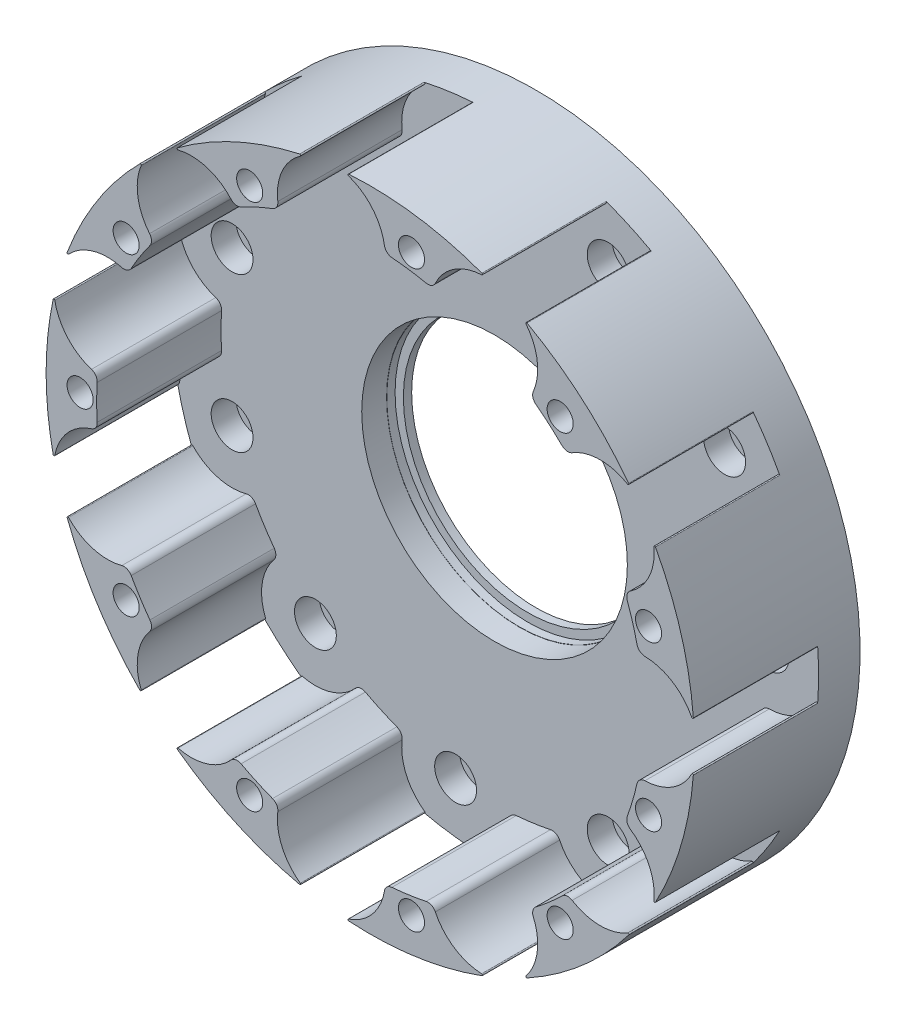
SolidWorks part; units mm, degrees
material "ABS"
ref_plane "Front Plane" through (0, 0, 0) normal (0, 0, 1) x (1, 0, 0)
ref_plane "Top Plane" through (0, 0, 0) normal (0, 1, 0) x (1, 0, 0)
ref_plane "Right Plane" through (0, 0, 0) normal (1, 0, 0) x (0, 0, -1)
sketch "Sketch1" plane through (0, 0, 0) normal (0, 0, 1) x (1, 0, 0)
  circle A0 centre (0, 0) radius 39.1
  circle A1 centre (0, 0) radius 33 construction
  circle A2 centre (33, 0) radius 2.525
  circle A3 centre (27.7614, -17.8411) radius 2.525
  circle A4 centre (13.7087, -30.0179) radius 2.525
  circle A5 centre (-4.6964, -32.6641) radius 2.525
  circle A6 centre (-21.6104, -24.9397) radius 2.525
  circle A7 centre (-31.6633, -9.2972) radius 2.525
  circle A8 centre (-31.6633, 9.2972) radius 2.525
  circle A9 centre (-21.6104, 24.9397) radius 2.525
  circle A10 centre (-4.6964, 32.6641) radius 2.525
  circle A11 centre (13.7087, 30.0179) radius 2.525
  circle A12 centre (27.7614, 17.8411) radius 2.525
  circle A13 centre (0, 0) radius 16.025
  point P28 (0, 0)
extrude "Boss-Extrude1" add sketch "Sketch1" along normal blind 3
sketch "Sketch2" plane through (0, 0, 0) normal (0, 0, -1) x (-1, 0, 0)
  circle A0 centre (0, 0) radius 16
  circle A1 centre (0, 0) radius 39.1
  circle A2 centre (0, 0) radius 39.1 construction
  dimension "D1" = 32
extrude "Boss-Extrude2" add sketch "Sketch2" along normal blind 2 contours A1 | A0
sketch "Sketch3" plane through (0, 0, 3) normal (0, 0, 1) x (1, 0, 0)
  circle A0 centre (33, 0) radius 1.6
  circle A1 centre (27.7614, -17.8411) radius 1.6
  circle A2 centre (13.7087, -30.0179) radius 1.6
  circle A3 centre (-4.6964, -32.6641) radius 1.6
  circle A4 centre (-21.6104, -24.9397) radius 1.6
  circle A5 centre (-31.6633, -9.2972) radius 1.6
  circle A6 centre (-31.6633, 9.2972) radius 1.6
  circle A7 centre (-21.6104, 24.9397) radius 1.6
  circle A8 centre (-4.6964, 32.6641) radius 1.6
  circle A9 centre (13.7087, 30.0179) radius 1.6
  circle A10 centre (27.7614, 17.8411) radius 1.6
  point P25 (0, 0)
  dimension "D1" = 3.2
  dimension "D2" = 11
sketch "Sketch4" plane through (0, 0, -2) normal (0, 0, -1) x (-1, 0, 0)
  circle A0 centre (0, 0) radius 16
  circle A1 centre (0, 0) radius 15
  dimension "D1" = 32
  dimension "D2" = 30
extrude "Boss-Extrude3" add sketch "Sketch4" against normal blind 1
sketch "Sketch5" plane through (0, 0, 3) normal (0, 0, 1) x (1, 0, 0)
  circle A0 centre (0, 0) radius 39.1
  circle A1 centre (0, 0) radius 39.1 construction
  arc A2 (1.7973, 32.951) -> (-11.0078, 31.1099) centre (-4.6964, 32.6641) ccw
  arc A3 (19.3266, 26.7485) -> (7.5589, 32.1226) centre (13.7087, 30.0179) ccw
  arc A4 (30.7199, 12.0535) -> (23.7258, 22.9366) centre (27.7614, 17.8411) ccw
  arc A5 (32.3598, -6.4684) -> (32.3598, 6.4684) centre (33, 0) ccw
  arc A6 (23.7258, -22.9366) -> (30.7199, -12.0535) centre (27.7614, -17.8411) ccw
  arc A7 (7.5589, -32.1226) -> (19.3266, -26.7485) centre (13.7087, -30.0179) ccw
  arc A8 (-11.0078, -31.1099) -> (1.7973, -32.951) centre (-4.6964, -32.6641) ccw
  arc A9 (-26.0797, -20.22) -> (-16.3027, -28.6918) centre (-21.6104, -24.9397) ccw
  arc A10 (-32.8714, -2.9104) -> (-29.2267, -15.3232) centre (-31.6633, -9.2972) ccw
  arc A11 (-29.2267, 15.3232) -> (-32.8714, 2.9104) centre (-31.6633, 9.2972) ccw
  arc A12 (-16.3027, 28.6918) -> (-26.0797, 20.22) centre (-21.6104, 24.9397) ccw
  arc A13 (-32.8714, 2.9104) -> (-32.8714, -2.9104) centre (0, 0) ccw
  arc A14 (-26.0797, 20.22) -> (-29.2267, 15.3232) centre (0, 0) ccw
  arc A15 (-11.0078, 31.1099) -> (-16.3027, 28.6918) centre (0, 0) ccw
  arc A16 (7.5589, 32.1226) -> (1.7973, 32.951) centre (0, 0) ccw
  arc A17 (23.7258, 22.9366) -> (19.3266, 26.7485) centre (0, 0) ccw
  arc A18 (32.3598, 6.4684) -> (30.7199, 12.0535) centre (0, 0) ccw
  arc A19 (30.7199, -12.0535) -> (32.3598, -6.4684) centre (0, 0) ccw
  arc A20 (19.3266, -26.7485) -> (23.7258, -22.9366) centre (0, 0) ccw
  arc A21 (1.7973, -32.951) -> (7.5589, -32.1226) centre (0, 0) ccw
  arc A22 (-16.3027, -28.6918) -> (-11.0078, -31.1099) centre (0, 0) ccw
  arc A23 (-29.2267, -15.3232) -> (-26.0797, -20.22) centre (0, 0) ccw
  point P30 (0, 0)
  dimension "D1" = 11
  dimension "D2" = 6.5
extrude "Boss-Extrude4" add sketch "Sketch5" along normal blind 15 contours A17 A4 A0 A3 | A18 A5 A0 A4 | A19 A6 A0 A5 | A20 A7 A0 A6 | A21 A8 A0 A7 | A22 A9 A0 A8 | A23 A10 A0 A9 | A13 A11 A0 A10 | A14 A12 A0 A11 | A15 A2 A0 A12 | A16 A3 A0 A2 region at (34.9977, 10.2762, 3) region at (34.9977, -10.2762, 3) region at (23.8862, 27.5661, 3) region at (23.8862, -27.5661, 3) region at (5.191, 36.1039, 3) region at (5.191, -36.1039, 3) region at (-15.1523, 33.179, 3) region at (-15.1523, -33.179, 3) region at (-30.6849, 19.72, 3) region at (-30.6849, -19.72, 3) region at (-36.4752, 0, 3)
fillet "Fillet1" radius 0.1 22 edges at (-7.9713, 38.2788, 10.5) (-27.401, 27.8926, 10.5) (-23.7091, 31.0916, 10.5) (-36.7548, 13.3378, 10.5) (-38.131, 8.6507, 10.5) (-38.131, -8.6507, 10.5) (-36.7548, -13.3378, 10.5) (-27.401, -27.8926, 10.5) (-23.7091, -31.0916, 10.5) (-7.9713, -38.2788, 10.5) (-3.136, -38.974, 10.5) (13.9892, -36.5118, 10.5) (18.4328, -34.4825, 10.5) (31.5083, -23.1525, 10.5) (34.1493, -19.043, 10.5) (39.0236, -2.4425, 10.5) (34.1493, 19.043, 10.5) (39.0236, 2.4425, 10.5) (31.5083, 23.1525, 10.5) (18.4328, 34.4825, 10.5) (13.9892, 36.5118, 10.5) (-3.136, 38.974, 10.5)
fillet "Fillet2" radius 1 22 edges at (-11.0078, -31.1099, 10.5) (-16.3027, -28.6918, 10.5) (23.7258, -22.9366, 10.5) (19.3266, -26.7485, 10.5) (7.5589, -32.1226, 10.5) (1.7973, -32.951, 10.5) (-29.2267, -15.3232, 10.5) (-26.0797, -20.22, 10.5) (-32.8714, -2.9104, 10.5) (-32.8714, 2.9104, 10.5) (-26.0797, 20.22, 10.5) (-29.2267, 15.3232, 10.5) (-16.3027, 28.6918, 10.5) (-11.0078, 31.1099, 10.5) (30.7199, -12.0535, 10.5) (32.3598, -6.4684, 10.5) (32.3598, 6.4684, 10.5) (30.7199, 12.0535, 10.5) (23.7258, 22.9366, 10.5) (19.3266, 26.7485, 10.5) (7.5589, 32.1226, 10.5) (1.7973, 32.951, 10.5)
sketch "Sketch7" plane through (0, 0, -2) normal (0, 0, -1) x (-1, 0, 0)
  line L0 (0, 0) -> (35, 0) construction
  circle A0 centre (35, 0) radius 1.575
  circle A1 centre (29.4439, -18.9224) radius 1.575
  circle A2 centre (14.5395, -31.8371) radius 1.575
  circle A3 centre (-4.981, -34.6438) radius 1.575
  circle A4 centre (-22.9201, -26.4512) radius 1.575
  circle A5 centre (-33.5823, -9.8606) radius 1.575
  circle A6 centre (-33.5823, 9.8606) radius 1.575
  circle A7 centre (-22.9201, 26.4512) radius 1.575
  circle A8 centre (-4.981, 34.6438) radius 1.575
  circle A9 centre (14.5395, 31.8371) radius 1.575
  circle A10 centre (29.4439, 18.9224) radius 1.575
  point P26 (0, 0)
  dimension "D2" = 3.15
  dimension "D1" = 35
  dimension "D3" = 11
extrude "Cut-Extrude1" cut sketch "Sketch7" against normal through all
sketch "Sketch8" plane through (0, 0, -2) normal (0, 0, -1) x (-1, 0, 0)
  line L0 (32.2124, -20.7016) -> (32.3689, -17.4145)
  line L1 (38.2909, 0) -> (36.6454, 2.85)
  line L2 (36.6454, 2.85) -> (33.3546, 2.85)
  line L3 (33.3546, 2.85) -> (31.7091, 0)
  line L4 (31.7091, 0) -> (33.3546, -2.85)
  line L5 (33.3546, -2.85) -> (36.6454, -2.85)
  line L6 (36.6454, -2.85) -> (38.2909, 0)
  line L7 (32.3689, -17.4145) -> (29.6005, -15.6353)
  line L8 (29.6005, -15.6353) -> (26.6754, -17.1432)
  line L9 (26.6754, -17.1432) -> (26.5188, -20.4304)
  line L10 (26.5188, -20.4304) -> (29.2873, -22.2096)
  line L11 (29.2873, -22.2096) -> (32.2124, -20.7016)
  line L12 (15.9066, -34.8306) -> (17.8155, -32.1499)
  line L13 (17.8155, -32.1499) -> (16.4484, -29.1564)
  line L14 (16.4484, -29.1564) -> (13.1724, -28.8436)
  line L15 (13.1724, -28.8436) -> (11.2635, -31.5243)
  line L16 (11.2635, -31.5243) -> (12.6306, -34.5178)
  line L17 (12.6306, -34.5178) -> (15.9066, -34.8306)
  line L18 (-5.4494, -37.9012) -> (-2.3942, -36.678)
  line L19 (-2.3942, -36.678) -> (-1.9259, -33.4206)
  line L20 (-1.9259, -33.4206) -> (-4.5127, -31.3864)
  line L21 (-4.5127, -31.3864) -> (-7.5678, -32.6095)
  line L22 (-7.5678, -32.6095) -> (-8.0362, -35.8669)
  line L23 (-8.0362, -35.8669) -> (-5.4494, -37.9012)
  line L24 (-25.0752, -28.9383) -> (-21.8438, -29.5611)
  line L25 (-21.8438, -29.5611) -> (-19.6887, -27.074)
  line L26 (-19.6887, -27.074) -> (-20.765, -23.9641)
  line L27 (-20.765, -23.9641) -> (-23.9965, -23.3413)
  line L28 (-23.9965, -23.3413) -> (-26.1516, -25.8284)
  line L29 (-26.1516, -25.8284) -> (-25.0752, -28.9383)
  line L30 (-36.7398, -10.7878) -> (-34.3581, -13.0588)
  line L31 (-34.3581, -13.0588) -> (-31.2005, -12.1316)
  line L32 (-31.2005, -12.1316) -> (-30.4247, -8.9335)
  line L33 (-30.4247, -8.9335) -> (-32.8064, -6.6625)
  line L34 (-32.8064, -6.6625) -> (-35.964, -7.5897)
  line L35 (-35.964, -7.5897) -> (-36.7398, -10.7878)
  line L36 (-36.7398, 10.7878) -> (-35.964, 7.5897)
  line L37 (-35.964, 7.5897) -> (-32.8064, 6.6625)
  line L38 (-32.8064, 6.6625) -> (-30.4247, 8.9335)
  line L39 (-30.4247, 8.9335) -> (-31.2005, 12.1316)
  line L40 (-31.2005, 12.1316) -> (-34.3581, 13.0588)
  line L41 (-34.3581, 13.0588) -> (-36.7398, 10.7878)
  line L42 (-25.0752, 28.9383) -> (-26.1516, 25.8284)
  line L43 (-26.1516, 25.8284) -> (-23.9965, 23.3413)
  line L44 (-23.9965, 23.3413) -> (-20.765, 23.9641)
  line L45 (-20.765, 23.9641) -> (-19.6887, 27.074)
  line L46 (-19.6887, 27.074) -> (-21.8438, 29.5611)
  line L47 (-21.8438, 29.5611) -> (-25.0752, 28.9383)
  line L48 (-5.4494, 37.9012) -> (-8.0362, 35.8669)
  line L49 (-8.0362, 35.8669) -> (-7.5678, 32.6095)
  line L50 (-7.5678, 32.6095) -> (-4.5127, 31.3864)
  line L51 (-4.5127, 31.3864) -> (-1.9259, 33.4206)
  line L52 (-1.9259, 33.4206) -> (-2.3942, 36.678)
  line L53 (-2.3942, 36.678) -> (-5.4494, 37.9012)
  line L54 (15.9066, 34.8306) -> (12.6306, 34.5178)
  line L55 (12.6306, 34.5178) -> (11.2635, 31.5243)
  line L56 (11.2635, 31.5243) -> (13.1724, 28.8436)
  line L57 (13.1724, 28.8436) -> (16.4484, 29.1564)
  line L58 (16.4484, 29.1564) -> (17.8155, 32.1499)
  line L59 (17.8155, 32.1499) -> (15.9066, 34.8306)
  line L60 (32.2124, 20.7016) -> (29.2873, 22.2096)
  line L61 (29.2873, 22.2096) -> (26.5188, 20.4304)
  line L62 (26.5188, 20.4304) -> (26.6754, 17.1432)
  line L63 (26.6754, 17.1432) -> (29.6005, 15.6353)
  line L64 (29.6005, 15.6353) -> (32.3689, 17.4145)
  line L65 (32.3689, 17.4145) -> (32.2124, 20.7016)
  circle A0 centre (35, 0) radius 2.85 construction
  circle A1 centre (29.4439, -18.9224) radius 2.85 construction
  circle A2 centre (14.5395, -31.8371) radius 2.85 construction
  circle A3 centre (-4.981, -34.6438) radius 2.85 construction
  circle A4 centre (-22.9201, -26.4512) radius 2.85 construction
  circle A5 centre (-33.5823, -9.8606) radius 2.85 construction
  circle A6 centre (-33.5823, 9.8606) radius 2.85 construction
  circle A7 centre (-22.9201, 26.4512) radius 2.85 construction
  circle A8 centre (-4.981, 34.6438) radius 2.85 construction
  circle A9 centre (14.5395, 31.8371) radius 2.85 construction
  circle A10 centre (29.4439, 18.9224) radius 2.85 construction
  point P91 (0, 0)
  dimension "D1" = 5.7
  dimension "D2" = 11
extrude "Cut-Extrude3" cut sketch "Sketch8" against normal blind 3
equation "\"RingPinShaft\"= 5.05"
equation "\"CenterBearingOut\"=32.05"
equation "\"OutputBearingOut\"=37.05"
equation "\"RingPostIn\"=5.15"
equation "\"CamBearingOut\"=15.1"
equation "\"DiskOutputShaft\"=10.1"
equation "\"CenterShaft\"=25.2"
equation "\"Eccentricity\"=2"
equation "\"CycCamShaft\"=10.05"
equation "\"m3Thru\"=3.15"
equation "\"m3Insert\"=4.2"
equation "\"MountingHoleDiam\"=35"
equation "\"D1@Sketch7\"=\"MountingHoleDiam\""
equation "\"D2@Sketch7\"=\"m3Thru\""
